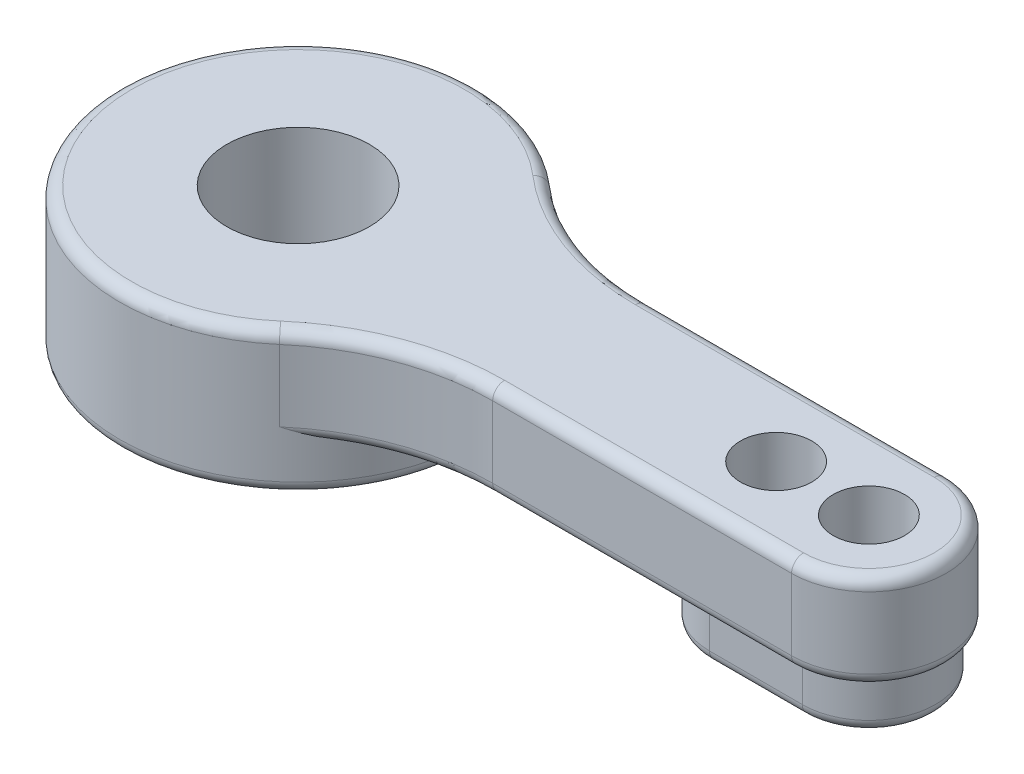
SolidWorks part; units mm, degrees
material "Nickel"
ref_plane "Front Plane" through (0, 0, 0) normal (0, 0, 1) x (1, 0, 0)
ref_plane "Top Plane" through (0, 0, 0) normal (0, 1, 0) x (1, 0, 0)
ref_plane "Right Plane" through (0, 0, 0) normal (1, 0, 0) x (0, 0, -1)
sketch "Sketch1" plane through (0, 0, 0) normal (0, 1, 0) x (1, 0, 0)
  circle A0 centre (0, 0) radius 7.5
  dimension "D1" = 15
extrude "Boss-Extrude1" add sketch "Sketch1" along normal blind 6
sketch "Sketch2" plane through (0, 6, 0) normal (0, 1, 0) x (1, 0, 0)
  line L0 (0, 0) -> (24, 0) construction
  line L1 (0, 3.25) -> (24, 3.25)
  line L2 (0, -3.25) -> (24, -3.25)
  arc A0 (0, 3.25) -> (0, -3.25) centre (0, 0) ccw
  arc A1 (24, -3.25) -> (24, 3.25) centre (24, 0) ccw
  point P3 (12, 0)
  dimension "D1" = 24
  dimension "D2" = 6.5
extrude "Boss-Extrude2" add sketch "Sketch2" against normal blind 4
sketch "Sketch4" plane through (0, 2, 0) normal (0, -1, 0) x (-1, 0, 0)
  line L0 (-24, 0) -> (-20.1, 0) construction
  line L1 (-24, 2.8) -> (-20.1, 2.8)
  line L2 (-24, -2.8) -> (-20.1, -2.8)
  arc A0 (-24, 2.8) -> (-24, -2.8) centre (-24, 0) ccw
  arc A1 (-20.1, -2.8) -> (-20.1, 2.8) centre (-20.1, 0) ccw
  point P4 (-22.05, 0)
  dimension "D1" = 3.9
  dimension "D2" = 2.8
extrude "Boss-Extrude3" add sketch "Sketch4" along normal blind 2
sketch "Sketch5" plane through (0, 0, 0) normal (0, -1, 0) x (1, 0, 0)
  circle A0 centre (24, 0) radius 1.5
  circle A1 centre (20.1, 0) radius 1.5
  circle A2 centre (0, 0) radius 3
  dimension "D1" = 3
  dimension "D2" = 6
extrude "Cut-Extrude1" cut sketch "Sketch5" against normal through all both and the other way through all
fillet "Fillet1" radius 10 2 edges at (6.7593, 4, -3.25) (6.7593, 4, 3.25)
fillet "Fillet2" radius 0.5 15 edges at (17.7159, 2, -3.25) (17.7159, 2, 3.25) (-7.5, 6, 0) (17.7159, 6, -3.25) (27.25, 6, 0) (7.9472, 2, -3.8768) (7.9472, 6, -3.8768) (7.9472, 6, 3.8768) (7.9472, 2, 3.8768) (17.7159, 6, 3.25) (22.05, 0, 2.8) (26.8, 0, 0) (22.05, 0, -2.8) (17.3, 0, 0) (0, 0, 7.5)
